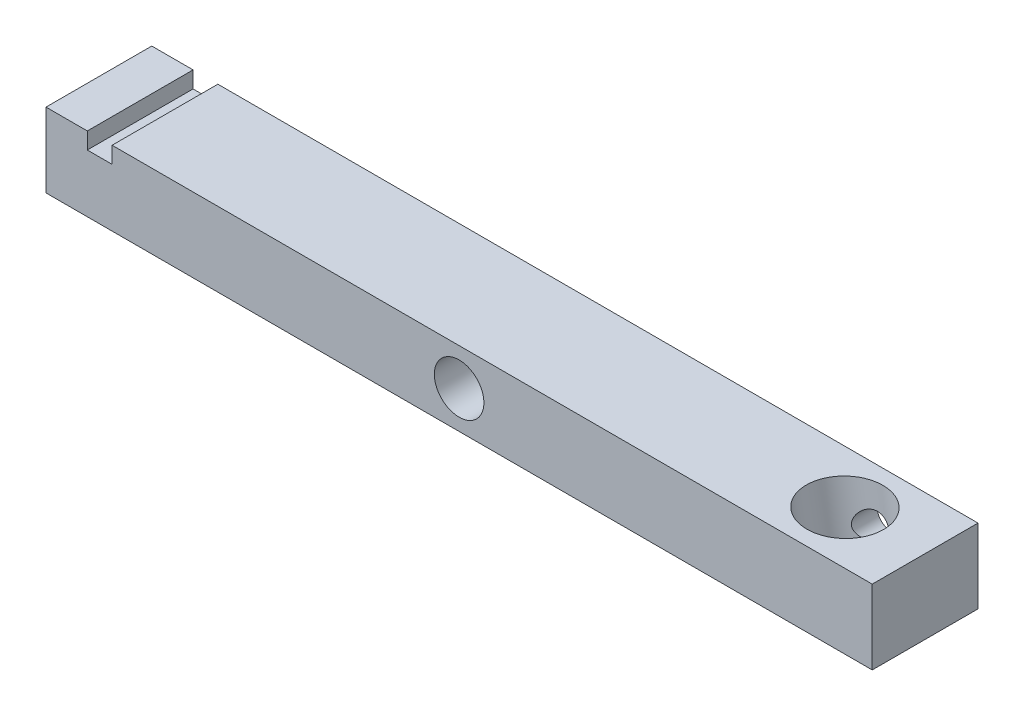
SolidWorks part; units mm, degrees
ref_plane "Front Plane" through (0, 0, 0) normal (0, 0, 1) x (1, 0, 0)
ref_plane "Top Plane" through (0, 0, 0) normal (0, 1, 0) x (1, 0, 0)
ref_plane "Right Plane" through (0, 0, 0) normal (1, 0, 0) x (0, 0, -1)
sketch "Sketch1" plane through (0, 0, 0) normal (0, 0, 1) x (1, 0, 0)
  line L1 (-63.5, -5.715) -> (63.5, -5.715)
  line L2 (-63.5, -5.715) -> (-63.5, 5.715)
  line L3 (-63.5, 5.715) -> (63.5, 5.715)
  line L4 (63.5, -5.715) -> (63.5, 5.715)
  line L5 (-63.5, -5.715) -> (63.5, 5.715) construction
  line L6 (-63.5, 5.715) -> (63.5, -5.715) construction
  point P0 (0, 0)
  dimension "D1" = 11.43
  dimension "D2" = 127
extrude "Boss-Extrude1" add sketch "Sketch1" along normal mid plane 16.256
sketch "Sketch6" plane through (0, 0, 8.128) normal (0, 0, 1) x (1, 0, 0)
  line L0 (-57.15, 5.715) -> (-57.15, 3.175)
  line L1 (43.18, -3.175) -> (43.18, -5.715)
  line L2 (-57.15, 3.175) -> (-53.34, 3.175)
  line L3 (-53.34, 3.175) -> (-53.34, 5.715)
  line L4 (-57.15, 5.715) -> (-53.34, 5.715)
  line L5 (63.5, 5.715) -> (-63.5, 5.715) construction
  line L6 (43.18, -5.715) -> (46.99, -5.715)
  line L7 (46.99, -5.715) -> (46.99, -3.175)
  line L8 (43.18, -3.175) -> (46.99, -3.175)
  line L9 (-63.5, -5.715) -> (63.5, -5.715) construction
  dimension "D4" = 2.54
  dimension "D1" = 53.34
  dimension "D2" = 2.54
  dimension "D3" = 57.15
  dimension "D5" = 43.18
  dimension "D6" = 3.81
extrude "Cut-Extrude1" cut sketch "Sketch6" against normal up to surface (16.256 mm away) contours L4 L3 L2 L0 up to face at (0, 0, -8.128)
sketch "Sketch12" plane through (0, 0, 8.128) normal (0, 0, 1) x (1, 0, 0)
  circle A0 centre (0, 0) radius 3.81
  dimension "D1" = 7.62
extrude "Cut-Extrude2" cut sketch "Sketch12" against normal up to surface (16.256 mm away) up to face at (-27.6225, 2.2225, -8.128)
ref_plane "Plane1" through (2.8921, -16.4018, 0) normal (0.1736, -0.9848, 0) x (0, 0, -1)
sketch "Sketch14" plane through (2.8921, -16.4018, 0) normal (0.1736, -0.9848, 0) x (0, 0, -1)
  line L0 (-8.128, 61.5429) -> (8.128, 61.5429) construction
  line L1 (0, -11.2201) -> (0, 68.737) construction
  circle A0 centre (0, 51.3829) radius 5.842
  dimension "D1" = 11.684
  dimension "D2" = 10.16
extrude "Cut-Extrude3" cut sketch "Sketch14" against normal blind 25.4
sketch "Sketch17" plane through (0, 0, -8.128) normal (0, 0, -1) x (-1, 0, 0)
  circle A0 centre (-50.0486, 0) radius 2.032
  dimension "D1" = 4.064
extrude "Cut-Extrude4" cut sketch "Sketch17" against normal up to surface (3.9622 mm away) up to face at (59.1154, -5.715, 0)
